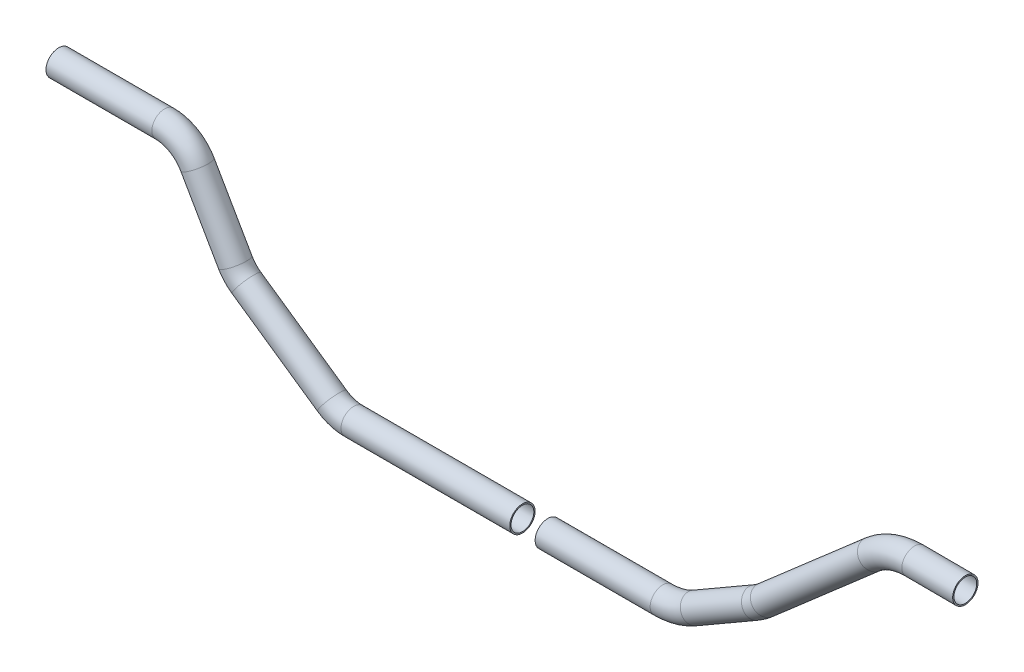
SolidWorks part; units mm, degrees
ref_plane "Front Plane" through (0, 0, 0) normal (0, 0, 1) x (1, 0, 0)
ref_plane "Top Plane" through (0, 0, 0) normal (0, 1, 0) x (1, 0, 0)
ref_plane "Right Plane" through (0, 0, 0) normal (1, 0, 0) x (0, 0, -1)
sketch "Sketch1" plane through (0, 0, 0) normal (0, 0, 1) x (1, 0, 0)
  line L0 (30, -35.3695) -> (130.7197, -35.3695)
  line L1 (155.7197, -28.6708) -> (203.9767, -0.8096)
  line L2 (211.794, 4.7687) -> (296.2345, 78.2282)
  line L3 (30, -25.3695) -> (30, -56.8695) construction
  line L4 (60, -25.3695) -> (0, -25.3695) construction
  line L5 (0, -35.3695) -> (59.9107, -35.3695) construction
  line L8 (329.2856, 90.5046) -> (369.358, 90.3173)
  arc A0 (296.2345, 78.2282) -> (329.2856, 90.5046) centre (329.0518, 40.5052) cw
  arc A1 (203.9767, -0.8096) -> (211.794, 4.7687) centre (178.9767, 42.4917) ccw
  arc A2 (130.7197, -35.3695) -> (155.7197, -28.6708) centre (130.7197, 14.6305) ccw
  point P12 (93.5879, -28.7751)
  point P13 (205.299, 6.5483)
  point P20 (369.358, 90.5046)
  dimension "D2" = 50
  dimension "D3" = 50
  dimension "D4" = 50
  dimension "D1" = 150
sketch "Sketch2" plane through (0, 0, 0) normal (0, 0, 1) x (1, 0, 0)
  line L0 (30, -35.3695) -> (-113.1376, -35.3695)
  line L1 (-130.2222, -30.0295) -> (-197.6569, 16.6897)
  line L2 (-206.5862, 26.4073) -> (-236.3347, 78.198)
  line L3 (-262.3487, 93.2556) -> (-345.8446, 93.2556)
  arc A0 (-113.1376, -35.3695) -> (-130.2222, -30.0295) centre (-113.1376, -5.3695) cw
  arc A1 (-197.6569, 16.6897) -> (-206.5862, 26.4073) centre (-180.5722, 41.3497) cw
  arc A2 (-236.3347, 78.198) -> (-262.3487, 93.2556) centre (-262.3487, 63.2556) ccw
  point P3 (-203.2171, 20.5418)
  point P7 (-245, 93.2837)
  point P8 (-374.2437, 93.7595)
  point P9 (-345.8446, 93.2556)
  dimension "D1" = 30
  dimension "D2" = 30
  dimension "D3" = 30
sweep "Sweep-Thin1" add path "Sketch1" circular profile diameter 20 parameters "D1"=1, "D3"=20
sweep "Sweep-Thin2" add path "Sketch2" circular profile diameter 20 parameters "D1"=1, "D3"=20
sketch "Sketch39" plane through (0, 0, 0) normal (0, 0, 1) x (1, 0, 0)
  line L0 (30, 0) -> (30, -52.4348) construction
  line L1 (40, -15.8293) -> (20, -15.8293)
  line L2 (20, -15.8293) -> (20, -52.4348)
  line L3 (20, -52.4348) -> (40, -52.4348)
  line L4 (40, -15.8293) -> (40, -52.4348)
  line L5 (30, -55.7519) -> (30, -53.5272) construction
  line L6 (10, -55.7519) -> (50, -55.7519) construction
  point P8 (30, -15.8293)
  dimension "D1" = 10
extrude "Cut-Extrude1" cut sketch "Sketch39" against normal through all both and the other way through all
ref_plane "Plane1" through (0, -35.3695, 0) normal (0, 1, 0) x (1, 0, 0)
